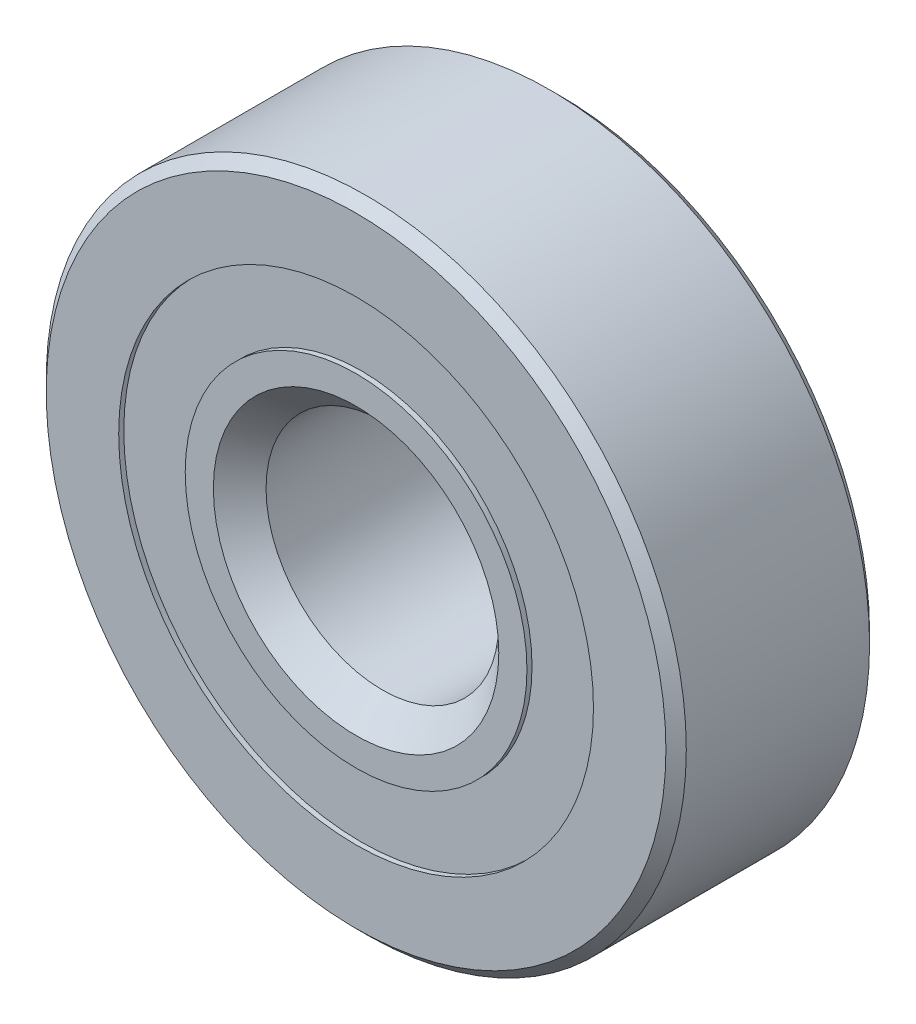
SolidWorks part; units mm, degrees
ref_plane "Front Plane" through (0, 0, 0) normal (0, 0, 1) x (1, 0, 0)
ref_plane "Top Plane" through (0, 0, 0) normal (0, 1, 0) x (1, 0, 0)
ref_plane "Right Plane" through (0, 0, 0) normal (1, 0, 0) x (0, 0, -1)
sketch "Sketch1" plane through (0, 0, 0) normal (1, 0, 0) x (0, 0, -1)
  line L0 (-3.5, 0) -> (3.5, 0) construction
  line L1 (0, 11) -> (0, -11) construction
  line L2 (3.15, 11) -> (-3.15, 11)
  line L3 (-3.15, 11) -> (-3.5, 10.65)
  line L4 (-3.5, 10.65) -> (-3.5, 8.1593)
  line L5 (-3.5, 8.1593) -> (-1.5556, 8.1593)
  line L6 (3.5, 8.1593) -> (1.5556, 8.1593)
  line L7 (3.5, 10.65) -> (3.5, 8.1593)
  line L8 (3.15, 11) -> (3.5, 10.65)
  line L9 (0, 11) -> (0, 7.5) construction
  line L10 (0, 7.5) -> (0, 4) construction
  arc A0 (-1.5556, 8.1593) -> (1.5556, 8.1593) centre (0, 7.5) cw
  point P14 (0, 4)
  dimension "Width" = 7
  dimension "OD" = 22
  dimension "D1" = 45
  dimension "D2" = 0.35
  dimension "D3" = 3.1111
  dimension "D4" = 0.6593
revolve "Revolve1" add sketch "Sketch1" angle 360 about L0
sketch "Sketch2" plane through (0, 0, 0) normal (1, 0, 0) x (0, 0, -1)
  line L0 (-3.325, 6.8407) -> (-1.5556, 6.8407)
  line L1 (-3.5, 10.65) -> (-3.5, -10.65) construction
  line L2 (-3.5, 5.8729) -> (-3.325, 5.8729) construction
  line L3 (-3.325, 5.6979) -> (-2.5323, 4.9052)
  line L4 (-2.5323, 4.9052) -> (0, 4.9052)
  line L5 (0, 11) -> (0, -11) construction
  line L6 (0, 4.9052) -> (0, 5.8105)
  line L7 (0, 5.8105) -> (0, 4) construction
  line L8 (-3.5, 6.8407) -> (-3.5, 4.9052) construction
  line L9 (-3.5, 4.9052) -> (-2.5323, 4.9052) construction
  line L10 (-3.325, 6.8407) -> (-3.325, 5.6979)
  line L11 (-3.325, 6.8407) -> (-3.325, 10.825) construction
  line L12 (-3.15, 11) -> (-3.5, 10.65) construction
  arc A0 (-1.5556, 6.8407) -> (0, 5.8105) centre (0, 7.5) ccw
  arc A1 (1.5556, 8.1593) -> (-1.5556, 8.1593) centre (0, 7.5) ccw construction
  circle A2 centre (0, 7.5) radius 1.6895 construction
  dimension "D1" = 45
revolve "Revolve2" [suppressed] add sketch "Sketch2" angle 360 about L0
sketch "Sketch3" plane through (0, 0, 0) normal (1, 0, 0) x (0, 0, -1)
  line L0 (-3.325, 5.6979) -> (-2.5323, 4.9052)
  line L1 (-2.5323, 4.9052) -> (0, 4.9052)
  line L2 (0, 4.9052) -> (0, 5.8105)
  line L3 (-3.5, 5.8729) -> (-3.5, 4.9052)
  line L4 (-3.5, 6.8407) -> (-3.5, 4.9052) construction
  line L5 (-3.5, 4.9052) -> (-2.5948, 4)
  line L6 (-2.5948, 4) -> (3.15, 4)
  line L7 (3.15, 11) -> (3.15, -11) construction
  line L8 (3.15, 4) -> (3.5, 4.35)
  line L9 (3.5, -10.65) -> (3.5, 10.65) construction
  line L10 (3.5, 4.35) -> (3.5, 6.8407)
  line L11 (3.5, 6.8407) -> (1.5556, 6.8407)
  line L12 (-3.5, 5.8729) -> (-3.325, 5.8729)
  line L13 (3.15, 11) -> (3.5, 10.65) construction
  line L14 (-3.325, 5.8729) -> (-3.325, 5.6979)
  circle A0 centre (0, 7.5) radius 1.6895 construction
  arc A1 (1.5556, 6.8407) -> (0, 5.8105) centre (0, 7.5) cw
revolve "Revolve3" add sketch "Sketch3" angle 360 about L0
sketch "Sketch4" plane through (0, 0, 0) normal (1, 0, 0) x (0, 0, -1)
  line L0 (-1.6895, 7.5) -> (1.6895, 7.5)
  circle A1 centre (0, 7.5) radius 1.6895 construction
  arc A2 (-1.6895, 7.5) -> (1.6895, 7.5) centre (0, 7.5) cw
  arc A3 (1.5556, 8.1593) -> (-1.5556, 8.1593) centre (0, 7.5) ccw construction
revolve "Revolve4" add sketch "Sketch4" angle 360 about L0
ref_axis "Axis1" through (0, 0, -3.5) along (0, 0, 1)
pattern_circular "CirPattern1" count 12 every 30 about axis through (0, 0, -3.5) along (0, 0, 1) of bodies 104
sketch "Sketch5" plane through (0, 0, 0) normal (1, 0, 0) x (0, 0, -1)
  line L0 (-3.5, 8.1593) -> (-1.5556, 8.1593) construction
  line L1 (-3.325, 8.1593) -> (-1.6895, 8.1593)
  line L2 (-3.325, 8.1593) -> (-3.325, 5.8729)
  line L3 (-3.325, 5.8729) -> (-1.6895, 5.8729)
  line L4 (-1.6895, 8.1593) -> (-1.6895, 5.8729)
  line L6 (-3.15, 11) -> (-3.5, 10.65) construction
  line L7 (0, 11) -> (0, 4) construction
  line L8 (3.325, 5.8729) -> (1.6895, 5.8729)
  line L9 (1.6895, 8.1593) -> (1.6895, 5.8729)
  line L10 (3.325, 8.1593) -> (1.6895, 8.1593)
  line L11 (3.325, 8.1593) -> (3.325, 5.8729)
  circle A0 centre (0, 7.5) radius 1.6895 construction
  point P10 (-3.325, 10.825)
revolve "Revolve5" add sketch "Sketch5" angle 360 about L0
equation "\"D2@Sketch1\" = \"Width@Sketch1\"*.05"
equation "\"D3@Sketch1\" = \"Width@Sketch1\"/2.25"
equation "\"D4@Sketch1\" = (((\"OD@Sketch1\"-\"Width@Sketch1\")/2)/3.25)/3.5"
equation "\"D2@CirPattern1\" = 360/\"Balls@CirPattern1\""
